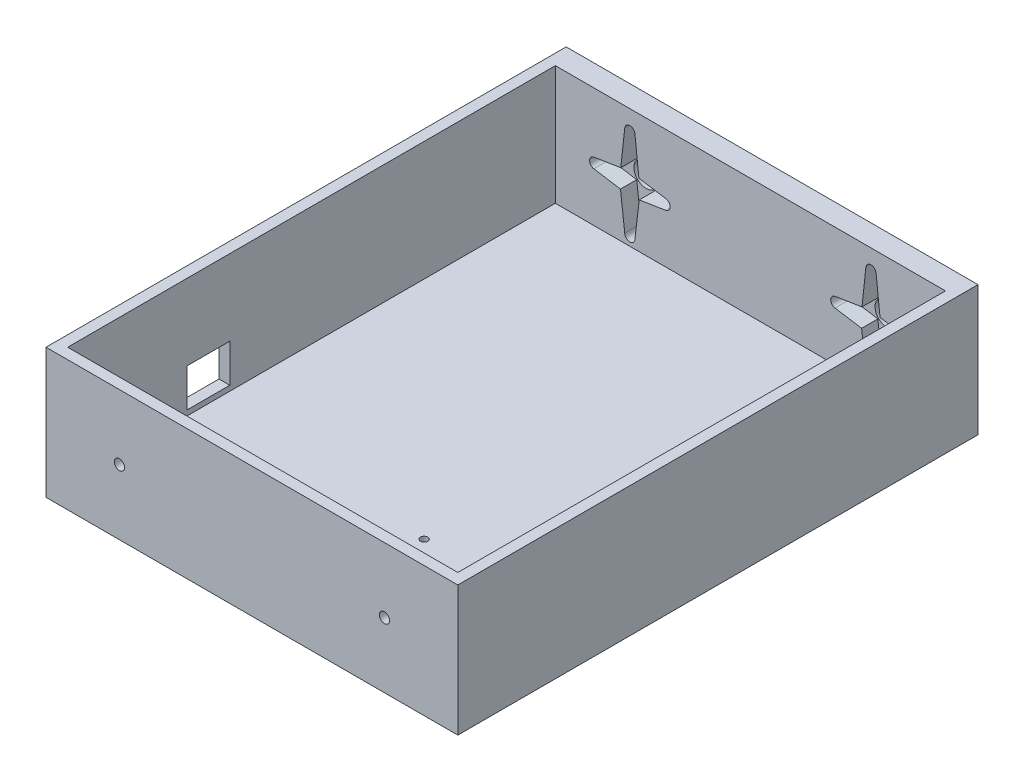
SolidWorks part; units mm, degrees
material "ABS"
ref_plane "Front" through (0, 0, 0) normal (0, 0, 1) x (1, 0, 0)
ref_plane "Top" through (0, 0, 0) normal (0, 1, 0) x (1, 0, 0)
ref_plane "Right" through (0, 0, 0) normal (1, 0, 0) x (0, 0, -1)
sketch "Sketch1" plane through (0, 0, 0) normal (0, 1, 0) x (1, 0, 0)
  line L1 (-60.325, 76.2) -> (60.325, 76.2)
  line L2 (-60.325, 76.2) -> (-60.325, -76.2)
  line L3 (-60.325, -76.2) -> (60.325, -76.2)
  line L4 (60.325, 76.2) -> (60.325, -76.2)
  line L5 (-60.325, 76.2) -> (60.325, -76.2) construction
  line L6 (-60.325, -76.2) -> (60.325, 76.2) construction
  line L11 (-57.15, 69.85) -> (57.15, 69.85)
  line L12 (-57.15, 69.85) -> (-57.15, -73.025)
  line L13 (-57.15, -73.025) -> (57.15, -73.025)
  line L14 (57.15, 69.85) -> (57.15, -73.025)
  point P0 (0, 0)
  point P6 (0, 0)
  dimension "D1" = 3.175
  dimension "D2" = 152.4
  dimension "D3" = 114.3
  dimension "D4" = 3.175
  dimension "D5" = 3.175
  dimension "D6" = 6.35
extrude "Boss-Extrude1" add sketch "Sketch1" along normal blind 3.175 contours L4 L3 L2 L1
extrude "Boss-Extrude2" add sketch "Sketch1<3>" along normal blind 38.1
sketch "Sketch1<3>" plane through (0, 0, 0) normal (0, 1, 0) x (1, 0, 0) same geometry as "Sketch1"
sketch "Sketch2" plane through (0, 0, 76.2) normal (0, 0, 1) x (1, 0, 0)
  line L0 (38.825, 19.05) -> (60.325, 19.05) construction
  line L1 (60.325, 38.1) -> (60.325, 0) construction
  circle A0 centre (38.825, 19.05) radius 1.5
  dimension "D2" = 3
  dimension "D1" = 21.5
extrude "Cut-Extrude1" cut sketch "Sketch2" against normal up to surface (3.175 mm away) up to face at (0, 20.6375, 73.025)
sketch "Sketch3" plane through (0, 0, -69.85) normal (0, 0, 1) x (1, 0, 0)
  line L0 (60.325, 19.05) -> (35.325, 19.05) construction
  line L1 (60.325, 38.1) -> (60.325, 0) construction
  line L2 (36.825, 5.8) -> (38.138, 16.8438)
  line L3 (33.825, 5.8) -> (32.5119, 16.8438)
  line L4 (32.6352, 21.4049) -> (33.8337, 32.4617)
  line L5 (38.0148, 21.4049) -> (36.8163, 32.4617)
  line L6 (24.7882, 17.5688) -> (33.1188, 16.2369)
  line L7 (24.7882, 20.5312) -> (33.1188, 21.863)
  line L9 (33.1188, 21.863) -> (33.1188, 16.2369) construction
  line L10 (37.5312, 21.863) -> (45.8618, 20.5312)
  line L11 (37.5312, 16.237) -> (45.8618, 17.5688)
  arc A0 (32.6352, 21.4049) -> (32.5119, 16.8438) centre (35.325, 19.05) ccw
  arc A1 (33.825, 5.8) -> (36.825, 5.8) centre (35.325, 5.8) ccw
  arc A2 (32.6352, 21.4049) -> (32.5119, 16.8438) centre (35.325, 19.05) ccw construction
  arc A10 (33.8337, 32.4617) -> (36.8163, 32.4617) centre (35.325, 32.3) cw
  arc A11 (38.138, 16.8438) -> (38.0148, 21.4049) centre (35.325, 19.05) ccw
  arc A12 (38.138, 16.8438) -> (38.0148, 21.4049) centre (35.325, 19.05) ccw construction
  arc A13 (24.7882, 20.5312) -> (24.7882, 17.5688) centre (25.025, 19.05) ccw
  arc A14 (37.5312, 21.863) -> (37.5312, 16.237) centre (35.325, 19.05) cw
  arc A15 (33.1188, 16.2369) -> (33.1188, 21.863) centre (35.325, 19.05) cw
  arc A16 (45.8618, 20.5312) -> (45.8618, 17.5688) centre (45.625, 19.05) cw
  circle A17 centre (35.325, 19.05) radius 3.575
  dimension "D1" = 7.15
  dimension "D3" = 3
  dimension "D6" = 14.75
  dimension "D7" = 3
  dimension "D2" = 25
  dimension "D4" = 14.75
  dimension "D5" = 5.6261
  dimension "D8" = 5.6261
  dimension "D9" = 11.8
extrude "Cut-Extrude8" cut sketch "Sketch3" against normal blind 4.7625 contours A16 L10 L5 A11 L2 L11 | A17 L10 L5 A10 L4 L7 | A17 L6 L3 A1 L2 L11 | L4 A15 L7 | L2 A14 L11 | L6 A15 L3 | L6 A15 L7 A13 | A14 L11 A16 L10 region at (35.325, 10.8168, -69.85) region at (37.9239, 16.4606, -69.85) region at (42.2416, 19.0536, -69.85) region at (32.7261, 16.4606, -69.85) region at (35.325, 27.3342, -69.85) region at (32.8048, 21.6911, -69.85)
extrude "Cut-Extrude9" cut sketch "Sketch3<8>" against normal through all contours A14 A17 A15 A0 A11 region at (35.325, 19.05, -69.85)
sketch "Sketch3<8>" plane through (0, 0, -69.85) normal (0, 0, 1) x (1, 0, 0) same geometry as "Sketch3"
mirror "Mirror1" about plane through (0, 0, 0) normal (1, 0, 0) of "Cut-Extrude9", "Cut-Extrude1", "Cut-Extrude8"
sketch "Sketch4" plane through (-57.15, 0, 0) normal (1, 0, 0) x (0, 0, -1)
  line L0 (-73.025, 15.876) -> (-38.025, 15.876) construction
  line L1 (-73.025, 38.1) -> (-73.025, 3.175) construction
  line L3 (-38.025, 15.876) -> (-25.525, 15.876)
  line L4 (-38.025, 15.876) -> (-38.025, 4.7)
  line L5 (-38.025, 4.7) -> (-25.525, 4.7)
  line L6 (-25.525, 15.876) -> (-25.525, 4.7)
  line L7 (76.2, 0) -> (-76.2, 0) construction
  dimension "D1" = 35
  dimension "D2" = 11.176
  dimension "D3" = 12.5
  dimension "D4" = 4.7
extrude "Cut-Extrude10" cut sketch "Sketch4" against normal up to next
sketch "Sketch5" plane through (0, 3.175, 0) normal (0, 1, 0) x (1, 0, 0)
  line L0 (-57.15, -34.596) -> (8.85, -34.596) construction
  line L1 (-57.15, 69.85) -> (-57.15, -73.025) construction
  line L2 (-60.325, -38.025) -> (-57.15, -38.025) construction
  line L3 (8.85, -34.596) -> (8.85, -62.6122) construction
  point P7 (8.85, -34.596)
  point P9 (8.85, -62.6122)
  dimension "D1" = 3.429
  dimension "D2" = 66
  dimension "D3" = 28.0162
hole_wizard "#2 Clearance Hole1" positions "3DSketch1" profile "Sketch7" hole size "#2" standard "ANSI Inch" end condition up to next
sketch3d "3DSketch1"
  point P0 (8.85, 3.175, 62.6122)
  point P3 (8.85, 3.175, 34.596)
sketch "Sketch7" plane through (8.85, 3.175, 62.6122) normal (1, 0, 0) x (0, 0, 1)
  line L0 (0, 0) -> (0, 3.175)
  line L1 (0, 3.175) -> (1.0795, 3.175)
  line L2 (1.0795, 3.175) -> (1.0795, 0)
  line L5 (1.0795, 0) -> (0, 0)
  line L11 (0, -6.35) -> (0, 107.95) construction
  dimension "Thru Hole Dia." = 2.159
  dimension "Thru Hole Depth" = 3.175
